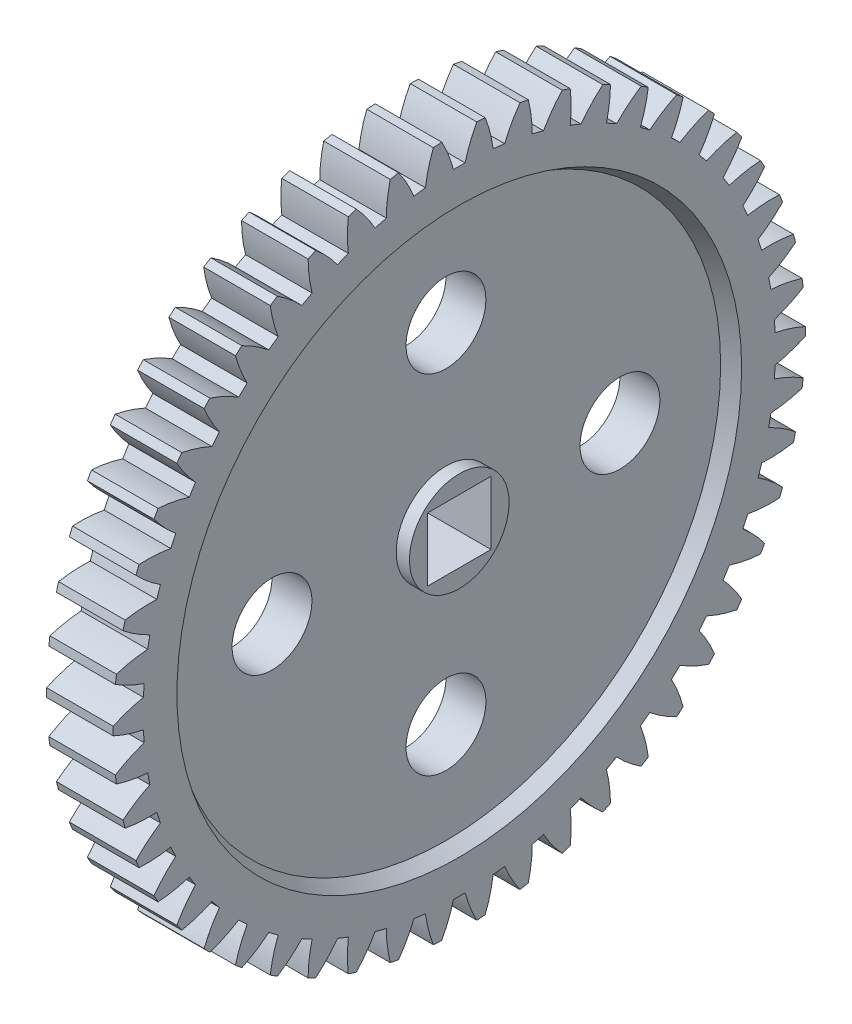
SolidWorks part; units mm, degrees
ref_plane "Plane1" through (0, 0, 0) normal (0, 0, 1) x (1, 0, 0)
ref_plane "Plane2" through (0, 0, 0) normal (0, 1, 0) x (1, 0, 0)
ref_plane "Plane3" through (0, 0, 0) normal (1, 0, 0) x (0, 0, -1)
sketch "HoldingSke" plane through (0, 0, 0) normal (0, 1, 0) x (1, 0, 0)
  line L0 (0, 0) -> (0.6428, -0.766)
  line L1 (-15, 0) -> (100, 0) construction
  line L2 (0, 0) -> (-2.1039, 2.3779)
  line L3 (0, 0) -> (-11.863, 4.5341)
  line L4 (0, 0) -> (5.5511, 6.6156)
  line L5 (0, 0) -> (-46.8476, -17.4728)
  line L6 (0, 0) -> (-4.1448, -2.7965)
  line L7 (-2.1039, 2.3779) -> (8.6586, 51.2059)
  line L8 (-76.2, 54.61) -> (-75.7, 54.61)
  line L9 (-71.009, 38.7566) -> (-53.1078, 45.2721)
  line L10 (-76.2, 71.12) -> (104.1128, 71.12)
  line L11 (0, 0) -> (-5, 0)
  line L12 (-76.2, 101.6) -> (-76.162, 101.6)
  line L13 (24.9733, 27.94) -> (52.9518, 28.4284)
  line L14 (24.9733, 27.94) -> (24.9743, 27.94)
  line L15 (24.9733, 27.94) -> (100.4006, 29.5858)
  line L16 (-63.627, -1) -> (-12.827, -1)
  circle A0 centre (0, 0) radius 1.5
  circle A1 centre (0, 0) radius 23.749
  circle A2 centre (0, 0) radius 37.5
  circle A3 centre (0, 0) radius 1.5
  dimension "MHD" = 47.498
  dimension "Hub_dia" = 75
  dimension "Bore" = 3
  dimension "MBD" = 3
  dimension "Num_teeth" = 50
  dimension "Pitch_radius" = 180.3128
  dimension "Pitch" = 1
  dimension "Width" = 5
  dimension "Overall_len" = 50
  dimension "Show_teeth" = 50
  dimension "Thickness" = 5
  dimension "OAL" = 50.0001
  dimension "T_dim" = 0.5
  dimension "Ap" = 20
  dimension "H" = 19.05
  dimension "Backlash" = 0.038
  dimension "Addendum_fac" = 1
  dimension "Dedendum_fac" = 1.25
  dimension "Clearance_fac" = 0.25
  dimension "Dedendum_add" = 0.001
  dimension "Module" = 1
sketch "BasProSke" plane through (0, 0, 0) normal (0, 1, 0) x (1, 0, 0)
  line L0 (-10, 0) -> (60, 0) construction
  line L1 (0, 0) -> (0, 26)
  line L2 (0, 0) -> (5, 0)
  line L3 (5, 0) -> (5, 26)
  line L4 (5, 26) -> (0, 26)
  dimension "Diameter" = 52
  dimension "Thickness" = 5
revolve "Base-Revolve" add sketch "BasProSke" angle 360 about L0
sketch "TooCutSke" plane through (0, 0, 0) normal (1, 0, 0) x (0, 0, -1)
  line L1 (0, 0) -> (0, 107) construction
  line L2 (0, 0) -> (-0.8518, 24.9855) construction
  line L3 (0, 0) -> (-3.1382, 49.8807) construction
  line L4 (-0.8518, 24.9855) -> (-1.5691, 24.9404) construction
  arc A0 (0.4377, 23.745) -> (-0.4377, 23.745) centre (0, 0) ccw
  arc A1 (1.3294, 25.9914) -> (-1.3294, 25.9914) centre (0, 0) ccw
  circle A2 centre (0, 0) radius 25 construction
  circle A3 centre (0, 0) radius 23.4923 construction
  arc A4 (-0.4377, 23.745) -> (-1.3294, 25.9914) centre (-10.1099, 21.2056) ccw
  arc A5 (1.3294, 25.9914) -> (0.4377, 23.745) centre (10.1099, 21.2056) ccw
  dimension "Root_dia" = 47.498
  dimension "Overcut_dia" = 52.0508
  dimension "Pitch_dia" = 50
  dimension "Base_dia" = 46.9846
  dimension "Flank_rad" = 10
  dimension "Half_ang" = 3.6
  dimension "Half_CT" = 0.7188
extrude "ToothCut" cut sketch "TooCutSke" along normal through all
fillet "Breaks" [suppressed] radius 0.02 tangent propagation no
fillet "RootFillets" [suppressed] radius 0.251
pattern_circular "TeethCuts" count 50 every 7.2 about axis through (-10, 0, 0) along (1, 0, 0) of "ToothCut", "RootFillets", "Breaks"
sketch "HubNeaOneSke" plane through (0, 0, 0) normal (-1, 0, 0) x (0, 0, 1)
  circle A0 centre (0, 0) radius 23.749
  dimension "Diameter" = 47.498
extrude "HubNearOne" [suppressed] add sketch "HubNeaOneSke" along normal blind 45.0001
sketch "HubNeaBotSke" plane through (0, 0, 0) normal (-1, 0, 0) x (0, 0, 1)
  circle A0 centre (0, 0) radius 23.749
  dimension "Diameter" = 47.498
extrude "HubNearBoth" [suppressed] add sketch "HubNeaBotSke" along normal blind 22.5
ref_plane "FarPln" through (5, 0, 0) normal (1, 0, 0) x (0, 0, -1)
sketch "HubFarSke" plane through (5, 0, 0) normal (1, 0, 0) x (0, 0, -1)
  circle A0 centre (0, 0) radius 23.749
  dimension "Diameter" = 47.498
extrude "HubFar" [suppressed] add sketch "HubFarSke" along normal blind 22.5
sketch "BorSke" plane through (0, 0, 0) normal (1, 0, 0) x (0, 0, -1)
  circle A0 centre (0, 0) radius 1.5875
  dimension "Diameter" = 3.175
extrude "Bore" cut sketch "BorSke" along normal mid plane 100.0001
sketch "KeySke" plane through (0, 0, 0) normal (1, 0, 0) x (0, 0, -1)
  line L0 (-0.6, 0) -> (-0.6, 2)
  line L1 (-0.6, 2) -> (0.6, 2)
  line L2 (0.6, 2) -> (0.6, 0)
  line L3 (0, 0) -> (0, 34) construction
  line L4 (-0.6, 0) -> (0.6, 0)
  dimension "Offset" = 2
  dimension "Width" = 1.2
extrude "Keyway" [suppressed] cut sketch "KeySke" along normal mid plane 100.0001
pattern_circular "Keyway2" [suppressed] count 2 every 90 about axis through (-10, 0, 0) along (1, 0, 0)
sketch "Sketch1" plane through (5, 0, 0) normal (1, 0, 0) x (0, 0, -1)
  circle A0 centre (0, 0) radius 21.211
extrude "Cut-Extrude1" cut sketch "Sketch1" against normal blind 1 draft 30
sketch "Sketch2" plane through (4, 0, 0) normal (1, 0, 0) x (0, 0, -1)
  circle A0 centre (0, 0) radius 3.7413
  circle A1 centre (0, 0) radius 1.5875
extrude "Boss-Extrude1" add sketch "Sketch2" along normal blind 1
ref_plane "Plane4" through (2.5, 0, 0) normal (1, 0, 0) x (0, 0, -1)
mirror "Mirror1" about plane through (2.5, 0, 0) normal (1, 0, 0) of "Cut-Extrude1", "Boss-Extrude1"
sketch "Sketch3" plane through (4, 0, 0) normal (1, 0, 0) x (0, 0, -1)
  circle A0 centre (0, 13.0706) radius 3
  dimension "D1" = 6
extrude "Cut-Extrude2" cut sketch "Sketch3" against normal through all
pattern_circular "CirPattern1" count 4 over 360 about axis through (50.0001, 0, 0) along (-1, 0, 0) of "Cut-Extrude2"
sketch "Sketch5" plane through (5, 0, 0) normal (1, 0, 0) x (0, 0, -1)
  line L1 (-2.3813, 2.3813) -> (2.3813, 2.3813)
  line L2 (-2.3813, 2.3813) -> (-2.3812, -2.3812)
  line L3 (-2.3812, -2.3812) -> (2.3813, -2.3812)
  line L4 (2.3813, 2.3813) -> (2.3813, -2.3812)
  line L5 (-2.3813, 2.3813) -> (2.3813, -2.3812) construction
  line L6 (-2.3812, -2.3812) -> (2.3813, 2.3813) construction
  point P0 (0, 0)
  dimension "D1" = 4.7625
  dimension "D2" = 4.7625
extrude "Cut-Extrude3" cut sketch "Sketch5" against normal through all
equation "' \"Module@HoldingSke\" = 6.35"
equation "' \"Num_teeth@HoldingSke\" = 12"
equation "' \"Ap@HoldingSke\" =  20"
equation "' \"Width@HoldingSke\" = 0.5 * 25.4"
equation "' \"Hub_dia@HoldingSke\"= 1 * 25.4"
equation "' \"Overall_len@HoldingSke\" = 1.0 * 25.4"
equation "' \"Bore@HoldingSke\" = 0.75 * 25.4"
equation "' \"T_dim@HoldingSke\" = 0.1 * 25.4"
equation "' \"Width@KeySke\" = 0.25 * 25.4"
equation "' \"Show_teeth@HoldingSke\" = 13"
equation "' \"Backlash@HoldingSke\" = 0.009 * 25.4"
equation "' \"Addendum_fac@HoldingSke\" = 1.0"
equation "' \"Dedendum_fac@HoldingSke\" = 1.25"
equation "' \"Dedendum_add@HoldingSke\" = 0.00005 * 25.4"
equation "' \"Clearance_fac@HoldingSke\" = 0.25"
equation "\"Pitch@HoldingSke\" = 1 / \"Module@HoldingSke\""
equation "\"Overcut_dia@TooCutSke\" = (\"Num_teeth@HoldingSke\" + 2 * \"Addendum_fac@HoldingSke\") / \"Pitch@HoldingSke\" + 0.002 * 25.4"
equation "\"Pitch_dia@TooCutSke\" = \"Num_teeth@HoldingSke\" / \"Pitch@HoldingSke\""
equation "\"Base_dia@TooCutSke\" = \"Num_teeth@HoldingSke\" / \"Pitch@HoldingSke\" * cos((\"Ap@HoldingSke\"  * 3.14159265 / 180))"
equation "\"Root_dia@TooCutSke\" = (\"Num_teeth@HoldingSke\" + 2) / \"Pitch@HoldingSke\" - 2 * (\"Addendum_fac@HoldingSke\" + \"Dedendum_fac@HoldingSke\") / \"Pitch@HoldingSke\" - \"Dedendum_add@HoldingSke\" * 2"
equation "\"Half_ang@TooCutSke\" = 180 / \"Num_teeth@HoldingSke\""
equation "\"Half_CT@TooCutSke\" = \"Num_teeth@HoldingSke\" / \"Pitch@HoldingSke\" * sin((3.14159265 / 2 / \"Num_teeth@HoldingSke\")) / 2 - 7 * \"Backlash@HoldingSke\" / 4"
equation "\"Flank_rad@TooCutSke\" = \"Num_teeth@HoldingSke\" / \"Pitch@HoldingSke\" / 5"
equation "\"Radius@RootFillets\" = \"Clearance_fac@HoldingSke\" / \"Pitch@HoldingSke\" + \"Dedendum_add@HoldingSke\""
equation "\"Break_rad@Breaks\" = 0.02 / \"Pitch@HoldingSke\""
equation "\"Thickness@HoldingSke\" = \"Width@HoldingSke\""
equation "\"OAL@HoldingSke\" = \"Thickness@HoldingSke\""
equation "\"MHD@HoldingSke\" = (\"Num_teeth@HoldingSke\" + 2) / \"Pitch@HoldingSke\" - 2 * (\"Addendum_fac@HoldingSke\" + \"Dedendum_fac@HoldingSke\")  / \"Pitch@HoldingSke\" - \"Dedendum_add@HoldingSke\" * 2"
equation "\"MBD@HoldingSke\" = (\"Num_teeth@HoldingSke\" + 2) / \"Pitch@HoldingSke\" - 2 * (\"Addendum_fac@HoldingSke\" + \"Dedendum_fac@HoldingSke\")  / \"Pitch@HoldingSke\" - \"Dedendum_add@HoldingSke\" * 2 - 0.002 * 25.4"
equation "\"MHD@HoldingSke\" = ((sgn( \"MHD@HoldingSke\" - \"Hub_dia@HoldingSke\" )-1)*( \"MHD@HoldingSke\" - \"Hub_dia@HoldingSke\" ))/-2+ \"Hub_dia@HoldingSke\""
equation "\"MBD@HoldingSke\" = ((sgn( \"MBD@HoldingSke\" - \"Bore@HoldingSke\" )-1)*( \"MBD@HoldingSke\" - \"Bore@HoldingSke\" ))/-2+ \"Bore@HoldingSke\""
equation "\"OAL@HoldingSke\" = ((sgn( \"OAL@HoldingSke\" - \"Overall_len@HoldingSke\" )+1)*( \"OAL@HoldingSke\" - \"Overall_len@HoldingSke\" ))/2 + \"Overall_len@HoldingSke\" + 0.000002 * 25.4"
equation "\"Num_teeth@TeethCuts\" = int( \"Show_teeth@HoldingSke\" ) + 1"
equation "\"Num_teeth@TeethCuts\" = ((sgn( \"Num_teeth@TeethCuts\" - \"Num_teeth@HoldingSke\" )-1)*( \"Num_teeth@TeethCuts\" - \"Num_teeth@HoldingSke\" ))/-2+ \"Num_teeth@HoldingSke\""
equation "\"Num_teeth@TeethCuts\" = ((sgn( \"Num_teeth@TeethCuts\" - 2.0)+1)*( \"Num_teeth@TeethCuts\" - 2.0))/2 +2.0"
equation "\"Angle@TeethCuts\" = 360.0 / \"Num_teeth@HoldingSke\""
equation "\"Diameter@BasProSke\" = (\"Num_teeth@HoldingSke\" + 2 * \"Addendum_fac@HoldingSke\") / \"Pitch@HoldingSke\""
equation "\"Thickness@BasProSke\"  = \"Thickness@HoldingSke\""
equation "' \"Fillet_rad@BasProSke\" =  \"Thickness@HoldingSke\" * 0.05"
equation "\"MHD@HoldingSke\" = ((sgn( \"MHD@HoldingSke\" - \"Root_dia@TooCutSke\" )-1)*( \"MHD@HoldingSke\" - \"Root_dia@TooCutSke\" ))/-2+ \"Root_dia@TooCutSke\""
equation "\"Diameter@HubNeaOneSke\" = \"MHD@HoldingSke\""
equation "\"Length@HubNearOne\" = \"OAL@HoldingSke\" - \"Thickness@BasProSke\""
equation "\"Diameter@HubNeaBotSke\" = \"MHD@HoldingSke\""
equation "\"Length@HubNearBoth\" = ( \"OAL@HoldingSke\" - \"Thickness@BasProSke\" ) / 2.0"
equation "\"Thickness@FarPln\" = \"Thickness@BasProSke\""
equation "\"Diameter@HubFarSke\" = \"MHD@HoldingSke\""
equation "\"Length@HubFar\" = ( \"OAL@HoldingSke\" - \"Thickness@BasProSke\" ) / 2.0"
equation "\"D1@Bore\" = \"OAL@HoldingSke\" * 2.0"
equation "\"D1@Keyway\" = \"OAL@HoldingSke\" * 2.0"
equation "\"Offset@KeySke\" = \"T_dim@HoldingSke\" + \"MBD@HoldingSke\" / 2.0"
